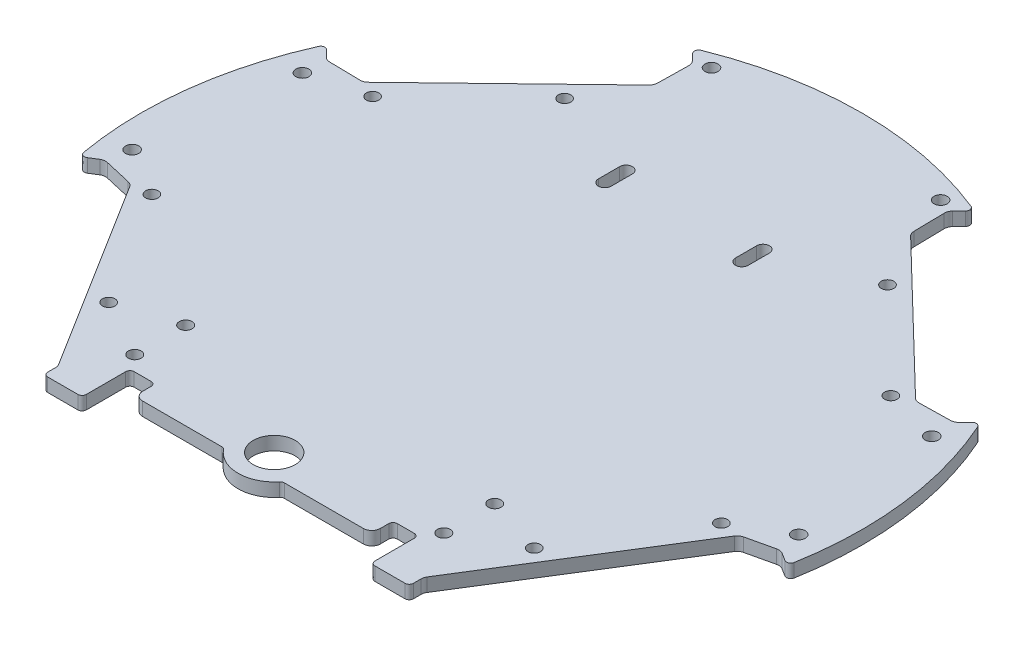
SolidWorks part; units mm, degrees
material "6061 Alloy"
ref_plane "Front Plane" through (0, 0, 0) normal (0, 0, 1) x (1, 0, 0)
ref_plane "Top Plane" through (0, 0, 0) normal (0, 1, 0) x (1, 0, 0)
ref_plane "Right Plane" through (0, 0, 0) normal (1, 0, 0) x (0, 0, -1)
sketch "Sketch1" plane through (0, 0, 0) normal (0, 1, 0) x (1, 0, 0)
  line L0 (0, 0) -> (0, -58.55) construction
  line L1 (-83.4462, -16.178) -> (-71.2857, -8.5793) construction
  line L6 (0, 0) -> (-59.046, 61.1439) construction
  line L7 (0, 0) -> (-72.0841, -45.0431) construction
  line L8 (-33.174, 78.2591) -> (-23.2129, 67.9442) construction
  line L9 (-72.0841, -45.0431) -> (-70.388, -43.9833) construction
  line L10 (-70.388, -43.9833) -> (-84.9608, -20.662) construction
  line L11 (-84.9608, -20.662) -> (-72.2401, -12.7132) construction
  line L12 (-72.2401, -12.7132) -> (-43.0945, -59.3558) construction
  line L13 (-43.0945, -59.3558) -> (-55.8152, -67.3046) construction
  line L14 (-55.8152, -67.3046) -> (-70.388, -43.9833) construction
  line L21 (-59.046, 61.1439) -> (-57.6566, 59.7052)
  line L22 (-77.4385, 40.6021) -> (-37.8748, 78.8083) construction
  line L23 (-73.9694, 32.6911) -> (-77.0537, 35.885)
  line L24 (-37.8748, 78.8083) -> (-27.4549, 68.0182) construction
  line L25 (-27.4549, 68.0182) -> (-67.0186, 29.812) construction
  line L26 (-67.0186, 29.812) -> (-77.4385, 40.6021) construction
  line L27 (-43.0945, -64.8266) -> (-34, -64.8266)
  line L33 (-86.5505, -18.1178) -> (-71.2857, -8.5793) construction
  line L34 (0, 0) -> (0, 50000) construction
  line L35 (0, 0) -> (-50000, 0) construction
  line L36 (-61.619, -58.55) -> (0, -58.55) construction
  line L38 (-67.0927, 25.57) -> (-79.5965, 38.5181) construction
  line L39 (-54.9774, -64.8266) -> (0, -64.8266) construction
  line L40 (-35.7168, 80.8923) -> (-23.2129, 67.9442) construction
  line L41 (-38.9606, -60.3102) -> (-54.2255, -69.8488) construction
  line L42 (-34, -58.55) -> (34, -58.55) construction
  line L43 (-43.0945, -64.8266) -> (-43.0945, -58.4123)
  line L45 (73.9694, 32.6911) -> (77.0537, 35.885)
  line L46 (-71.2857, -8.5793) -> (-38.9606, -60.3102) construction
  line L47 (83.4462, -16.178) -> (79.6809, -13.8252)
  line L48 (69.4846, -16.1792) -> (43.0945, -58.4123)
  line L49 (43.0945, -64.8266) -> (43.0945, -58.4123)
  line L50 (43.0945, -64.8266) -> (34, -64.8266)
  line L51 (34, -58.55) -> (34, -64.8266)
  line L52 (0, 0) -> (72.0841, -45.0431) construction
  line L53 (0, 0) -> (59.046, 61.1439) construction
  line L54 (-30.0897, 75.0653) -> (-30.2847, 63.8954)
  line L55 (-62.7996, 32.4961) -> (-30.2847, 63.8954)
  line L56 (-30.0897, 75.0653) -> (-33.174, 78.2591)
  line L57 (73.9694, 32.6911) -> (77.0537, 35.885)
  line L58 (30.0897, 75.0653) -> (33.174, 78.2591)
  line L59 (-34, -58.55) -> (-34, -53.55)
  line L60 (62.7996, 32.4961) -> (30.2847, 63.8954)
  line L61 (-73.9694, 32.6911) -> (-62.7996, 32.4961)
  line L62 (-77.0537, 35.885) -> (-67.0927, 25.57) construction
  line L63 (-83.4462, -16.178) -> (-79.6809, -13.8252)
  line L64 (-79.6809, -13.8252) -> (-69.4846, -16.1792)
  line L65 (-69.4846, -16.1792) -> (-43.0945, -58.4123)
  line L66 (-27.4549, 68.0182) -> (-23.2129, 67.9442) construction
  line L67 (-72.2401, -12.7132) -> (-71.2857, -8.5793) construction
  line L68 (30.0897, 75.0653) -> (30.2847, 63.8954)
  line L69 (73.9694, 32.6911) -> (62.7996, 32.4961)
  line L70 (-34, -58.55) -> (-34, -64.8266)
  line L71 (79.6809, -13.8252) -> (69.4846, -16.1792)
  line L72 (-34, -53.55) -> (-28, -53.55)
  line L73 (-28, -53.55) -> (-28, -58.55)
  line L74 (-28, -58.55) -> (28, -58.55)
  line L75 (28, -53.55) -> (28, -58.55)
  line L76 (34, -53.55) -> (28, -53.55)
  line L77 (34, -58.55) -> (34, -53.55)
  line L97 (-23.2129, 67.9442) -> (-67.0927, 25.57) construction
  circle A0 centre (0, 0) radius 85 construction
  circle A1 centre (0, 0) radius 90 construction
  arc A51 (-77.0537, 35.885) -> (-83.4462, -16.178) centre (0, 0) ccw
  arc A52 (77.0537, 35.885) -> (83.4462, -16.178) centre (0, 0) cw
  arc A54 (-33.174, 78.2591) -> (33.174, 78.2591) centre (0, 0) cw
  point P29 (-31.6318, 76.6622)
  point P33 (-47.2368, 48.9151)
  point P34 (31.6318, 76.6622)
  point P35 (-57.6673, -36.0345)
  point P85 (-57.6566, 59.7052)
  dimension "D2" = 58
  dimension "D12" = 170
  dimension "D14" = 34
  dimension "D15" = 3
  dimension "D3" = 180
  dimension "D4" = 64.8266
  dimension "D5" = 44
  dimension "D6" = 15
  dimension "D7" = 55
  dimension "D8" = 58.55
  dimension "D9" = 2
  dimension "D11" = 2
  dimension "D16" = 7
  dimension "D17" = 7
  dimension "D18" = 0.5
  dimension "D19" = 1
  dimension "D20" = 6
  dimension "D21" = 5
extrude "Boss-Extrude4" add sketch "Sketch1" along normal blind 3.175 contours A0 L70 region at (0, 0, -6.6852)
ref_point "Rear_Axle_Center (L)"
ref_axis "Rear_Axle_Proj (L)" through (46.5421, 0, -48.1958) along (0, 1, 0)
ref_point "Front_Axle_Center (L)"
ref_axis "Front_Axle_Proj (L)" through (57.2432, 0, 35.7696) along (0, 1, 0)
ref_point "Front_Axle_Center (R)"
ref_axis "Front_Axle_Proj (R)" through (-57.2432, 0, 35.7696) along (0, 1, 0)
ref_point "Read_Axle_Center (R)"
ref_axis "Rear_Axle_Proj (R)" through (-46.5421, 0, -48.1958) along (0, 1, 0)
sketch "Sketch17" plane through (0, 3.175, 0) normal (0, 1, 0) x (1, 0, 0)
  line L0 (0, -53.55) -> (0, -58.55) construction
  line L1 (-28, -58.55) -> (28, -58.55) construction
  circle A0 centre (0, -53.55) radius 8.5
  dimension "D1" = 17
  dimension "D2" = 5
extrude "Boss-Extrude5" add sketch "Sketch17" against normal up to surface (3.175 mm away) up to face at (0, 0, 5.182)
ref_plane "Plane1" through (0, 0, 10) normal (0, 0, 1) x (1, 0, 0)
hole_wizard "M3 Clearance Hole3" positions "Sketch18" profile "Sketch19" hole size "M3" standard "ANSI Metric" end condition through all
sketch "Sketch18" plane through (0, 0, 0) normal (0, -1, 0) x (-1, 0, 0)
  line L0 (-36.415, -50) -> (-36.415, -38) construction
  line L3 (0, 0) -> (0, -38) construction
  line L4 (36.415, -50) -> (36.415, -38) construction
  line L6 (0, -38) -> (36.415, -38) construction
  line L8 (0, -38) -> (-36.415, -38) construction
  point P1 (36.415, -50)
  point P3 (36.415, -38)
  point P5 (-36.415, -50)
  point P33 (-36.415, -38)
  dimension "D1" = 12
  dimension "D2" = 36.415
  dimension "D3" = 36.415
  dimension "D4" = 38
sketch "Sketch19" plane through (-36.415, 0, 50) normal (1, 0, 0) x (0, 0, -1)
  line L0 (0, 0) -> (0, 3.175)
  line L1 (0, 3.175) -> (1.5, 3.175)
  line L2 (1.5, 3.175) -> (1.5, 0)
  line L5 (1.5, 0) -> (0, 0)
  line L11 (0, -6.35) -> (0, 107.95) construction
  dimension "Thru Hole Dia." = 3
  dimension "Thru Hole Depth" = 3.175
hole_wizard "M3 Clearance Hole1" positions "Sketch11" profile "Sketch12" hole size "M3" standard "ANSI Metric" end condition through all
sketch "Sketch11" plane through (0, 3.175, 0) normal (0, 1, 0) x (1, 0, 0)
  line L0 (83.4462, -16.178) -> (79.6809, -13.8252) construction
  line L2 (73.9694, 32.6911) -> (77.0537, 35.885) construction
  line L4 (-73.9694, 32.6911) -> (-77.0537, 35.885) construction
  line L6 (0, 0) -> (0, -50000) construction
  line L7 (78.4111, 9.6277) -> (84.3664, 10.3589) construction
  line L10 (74.155, 27.2403) -> (78.5423, -8.4914) construction
  line L12 (78.4111, 9.6277) -> (76.3487, 9.3744) construction
  arc A7 (77.964, -12.7523) -> (72.563, 31.2347) centre (0, 0) ccw construction
  arc A13 (-77.964, -12.7523) -> (-72.563, 31.2347) centre (0, 0) cw construction
  arc A17 (83.4462, -16.178) -> (77.0537, 35.885) centre (0, 0) ccw construction
  point P34 (78.5423, -8.4914)
  point P66 (74.155, 27.2403)
  point P70 (-74.155, 27.2403)
  point P71 (-78.5423, -8.4914)
  dimension "D1" = 6
  dimension "D2" = 36
sketch "Sketch12" plane through (-78.5423, 3.175, 8.4914) normal (1, 0, 0) x (0, 0, 1)
  line L0 (0, 0) -> (0, 3.175)
  line L1 (0, 3.175) -> (1.55, 3.175)
  line L2 (1.55, 3.175) -> (1.55, 0)
  line L5 (1.55, 0) -> (0, 0)
  line L11 (0, -6.35) -> (0, 107.95) construction
  dimension "Thru Hole Dia." = 3.1
  dimension "Thru Hole Depth" = 3.175
hole_wizard "M3 Clearance Hole4" positions "Sketch9" profile "Sketch10" hole size "M3" standard "ANSI Metric" end condition through all
sketch "Sketch9" plane through (0, 0, 0) normal (0, -1, 0) x (-1, 0, 0)
  line L0 (0, 0) -> (0, 63.4318) construction
  line L1 (-38.0437, 52.9272) -> (38.0437, 52.9272) construction
  line L3 (61.0625, 30.6981) -> (-61.0625, 30.6981) construction
  line L4 (-67.0993, -15.2789) -> (67.0993, -15.2789) construction
  line L5 (50.1419, -42.4164) -> (-50.1419, -42.4164) construction
  line L6 (-61.0625, 30.6981) -> (-38.0437, 52.9272) construction
  line L7 (38.0437, 52.9272) -> (61.0625, 30.6981) construction
  line L8 (67.0993, -15.2789) -> (50.1419, -42.4164) construction
  line L9 (-50.1419, -42.4164) -> (-67.0993, -15.2789) construction
  line L10 (0, 0) -> (-44.8055, 46.3974) construction
  line L11 (0, 0) -> (44.8055, 46.3974) construction
  line L12 (0, 0) -> (-96.9468, 0) construction
  line L14 (-55.1231, -34.4448) -> (0, 0) construction
  line L15 (0, 0) -> (55.1231, -34.4448) construction
  line L18 (-69.4846, -16.1792) -> (-43.0945, -58.4123) construction
  line L19 (-62.7996, 32.4961) -> (-30.2847, 63.8954) construction
  point P0 (-67.0993, -15.2789)
  point P2 (-50.1419, -42.4164)
  point P9 (-61.0625, 30.6981)
  point P11 (-38.0437, 52.9272)
  point P30 (50.1419, -42.4164)
  point P31 (67.0993, -15.2789)
  point P32 (38.0437, 52.9272)
  point P33 (61.0625, 30.6981)
  dimension "D9" = 46
  dimension "D10" = 46
  dimension "D11" = 32
  dimension "D12" = 32
  dimension "D7" = 58
  dimension "D5" = 32
  dimension "D6" = 2.5
  dimension "D8" = 9.4
  dimension "D2" = 44
  dimension "D3" = 32
  dimension "D4" = 2.5
  dimension "D13" = 9.4
sketch "Sketch10" plane through (67.0993, 0, 15.2789) normal (1, 0, 0) x (0, 0, -1)
  line L0 (0, 0) -> (0, 3.175)
  line L1 (0, 3.175) -> (1.475, 3.175)
  line L2 (1.475, 3.175) -> (1.475, 0)
  line L5 (1.475, 0) -> (0, 0)
  line L11 (0, -6.35) -> (0, 107.95) construction
  dimension "Thru Hole Dia." = 2.95
  dimension "Thru Hole Depth" = 3.175
hole_wizard "M3 Clearance Hole2" positions "Sketch13" profile "Sketch14" hole size "M3" standard "ANSI Metric" end condition through all
sketch "Sketch13" plane through (0, 3.175, 0) normal (0, 1, 0) x (1, 0, 0)
  line L0 (0, 0) -> (0, 85) construction
  line L2 (-24, 47) -> (-24, 81) construction
  line L3 (-24, 47) -> (24, 47) construction
  line L4 (-24, 81) -> (24, 81) construction
  line L5 (24, 47) -> (24, 81) construction
  line L6 (-24, 47) -> (24, 81) construction
  line L7 (-24, 81) -> (24, 47) construction
  line L8 (-38.0437, 52.9272) -> (-61.0625, 30.6981) construction
  line L10 (-36.307, 51.1289) -> (-59.3259, 28.8998) construction
  line L11 (-16.3488, 39.8187) -> (-31.6313, 55.6441) construction
  line L12 (-16.3488, 39.8187) -> (-48.7191, 8.559) construction
  line L13 (-31.6313, 55.6441) -> (-64.0016, 24.3845) construction
  line L14 (-48.7191, 8.559) -> (-64.0016, 24.3845) construction
  line L15 (-16.3488, 39.8187) -> (-64.0016, 24.3845) construction
  line L16 (-31.6313, 55.6441) -> (-48.7191, 8.559) construction
  line L17 (-49.5531, 41.8127) -> (-40.1752, 32.1016) construction
  line L18 (-27, 76.4978) -> (-27, 80.5978) construction
  arc A0 (33.174, 78.2591) -> (-33.174, 78.2591) centre (0, 0) ccw construction
  circle A1 centre (-16.2162, 44) radius 3 construction
  circle A2 centre (-27, 76.4978) radius 3 construction
  point P65 (0, 64)
  point P181 (-27, 76.4978)
  point P184 (27, 76.4978)
  dimension "D7" = 6
  dimension "D1" = 48
  dimension "D2" = 34
  dimension "D3" = 4
  dimension "D5" = 45
  dimension "D6" = 22
  dimension "D8" = 4.1
  dimension "D4" = 2.5
sketch "Sketch14" plane through (27, 3.175, -76.4978) normal (1, 0, 0) x (0, 0, 1)
  line L0 (0, 0) -> (0, 3.175)
  line L1 (0, 3.175) -> (1.55, 3.175)
  line L2 (1.55, 3.175) -> (1.55, 0)
  line L5 (1.55, 0) -> (0, 0)
  line L11 (0, -6.35) -> (0, 107.95) construction
  dimension "Thru Hole Dia." = 3.1
  dimension "Thru Hole Depth" = 3.175
sketch "Sketch20" plane through (0, 3.175, 0) normal (0, 1, 0) x (1, 0, 0)
  line L0 (-16.1485, 45.5) -> (-16.1485, 40.5) construction
  line L1 (-14.6485, 45.5) -> (-14.6485, 40.5)
  line L2 (-17.6485, 45.5) -> (-17.6485, 40.5)
  line L3 (0, 0) -> (0, 85) construction
  line L5 (16.1485, 45.5) -> (16.1485, 40.5) construction
  line L6 (14.6485, 45.5) -> (14.6485, 40.5)
  line L7 (17.6485, 45.5) -> (17.6485, 40.5)
  arc A0 (-14.6485, 45.5) -> (-17.6485, 45.5) centre (-16.1485, 45.5) ccw
  arc A1 (-17.6485, 40.5) -> (-14.6485, 40.5) centre (-16.1485, 40.5) ccw
  arc A5 (33.174, 78.2591) -> (-33.174, 78.2591) centre (0, 0) ccw construction
  arc A7 (14.6485, 45.5) -> (17.6485, 45.5) centre (16.1485, 45.5) cw
  arc A8 (17.6485, 40.5) -> (14.6485, 40.5) centre (16.1485, 40.5) cw
  point P2 (-16.1485, 43)
  point P16 (16.1485, 43)
  dimension "D1" = 45.5
  dimension "D2" = 3
  dimension "D3" = 5
  dimension "D4" = 16.1485
extrude "Cut-Extrude1" cut sketch "Sketch20" against normal through all
sketch "Sketch22" plane through (0, 3.175, 0) normal (0, 1, 0) x (1, 0, 0)
  line L0 (-56.2896, -37.2958) -> (-57.6464, -38.1436) construction
  line L1 (-69.4846, -16.1792) -> (-43.0945, -58.4123) construction
  line L2 (-43.0945, -64.8266) -> (-43.0945, -58.4123) construction
  line L3 (30.2452, 66.1578) -> (65.062, 32.5356)
  line L4 (71.6894, -15.6702) -> (43.0945, -61.4316)
  line L28 (-30.2452, 66.1578) -> (-65.062, 32.5356)
  line L29 (-71.6894, -15.6702) -> (-43.0945, -61.4316)
  line L30 (-79.6809, -13.8252) -> (-69.4846, -16.1792) construction
  line L31 (0, 85) -> (0, -53.55) construction
  line L32 (-46.5421, 48.1958) -> (-47.6536, 49.3467) construction
  line L56 (-28, -58.55) -> (-6.8739, -58.55)
  line L57 (6.8739, -58.55) -> (28, -58.55)
  line L58 (28, -58.55) -> (28, -53.55)
  line L59 (28, -53.55) -> (34, -53.55)
  line L60 (34, -53.55) -> (34, -64.8266)
  line L61 (34, -64.8266) -> (43.0945, -64.8266)
  line L62 (43.0945, -64.8266) -> (43.0945, -58.4123)
  line L63 (43.0945, -58.4123) -> (69.4846, -16.1792)
  line L64 (69.4846, -16.1792) -> (79.6809, -13.8252)
  line L65 (79.6809, -13.8252) -> (83.4462, -16.178)
  line L66 (77.0537, 35.885) -> (73.9694, 32.6911)
  line L67 (73.9694, 32.6911) -> (62.7996, 32.4961)
  line L68 (62.7996, 32.4961) -> (30.2847, 63.8954)
  line L69 (30.2847, 63.8954) -> (30.0897, 75.0653)
  line L70 (30.0897, 75.0653) -> (33.174, 78.2591)
  line L71 (-33.174, 78.2591) -> (-30.0897, 75.0653)
  line L72 (-30.0897, 75.0653) -> (-30.2847, 63.8954)
  line L73 (-30.2847, 63.8954) -> (-62.7996, 32.4961)
  line L74 (-62.7996, 32.4961) -> (-73.9694, 32.6911)
  line L75 (-73.9694, 32.6911) -> (-77.0537, 35.885)
  line L76 (-83.4462, -16.178) -> (-79.6809, -13.8252)
  line L77 (-79.6809, -13.8252) -> (-69.4846, -16.1792)
  line L78 (-69.4846, -16.1792) -> (-43.0945, -58.4123)
  line L79 (-43.0945, -58.4123) -> (-43.0945, -64.8266)
  line L80 (-43.0945, -64.8266) -> (-34, -64.8266)
  line L81 (-34, -64.8266) -> (-34, -53.55)
  line L82 (-34, -53.55) -> (-28, -53.55)
  line L83 (-28, -53.55) -> (-28, -58.55)
  line L84 (-28, -58.55) -> (-6.8739, -58.55)
  line L85 (6.8739, -58.55) -> (28, -58.55)
  line L86 (28, -58.55) -> (28, -53.55)
  line L87 (28, -53.55) -> (34, -53.55)
  line L88 (34, -53.55) -> (34, -64.8266)
  line L89 (34, -64.8266) -> (43.0945, -64.8266)
  line L90 (43.0945, -64.8266) -> (43.0945, -58.4123)
  line L91 (43.0945, -58.4123) -> (69.4846, -16.1792)
  line L92 (69.4846, -16.1792) -> (79.6809, -13.8252)
  line L93 (79.6809, -13.8252) -> (83.4462, -16.178)
  line L94 (77.0537, 35.885) -> (73.9694, 32.6911)
  line L95 (73.9694, 32.6911) -> (62.7996, 32.4961)
  line L96 (62.7996, 32.4961) -> (30.2847, 63.8954)
  line L97 (30.2847, 63.8954) -> (30.0897, 75.0653)
  line L98 (30.0897, 75.0653) -> (33.174, 78.2591)
  line L99 (-33.174, 78.2591) -> (-30.0897, 75.0653)
  line L100 (-30.0897, 75.0653) -> (-30.2847, 63.8954)
  line L101 (-30.2847, 63.8954) -> (-62.7996, 32.4961)
  line L102 (-62.7996, 32.4961) -> (-73.9694, 32.6911)
  line L103 (-73.9694, 32.6911) -> (-77.0537, 35.885)
  line L104 (-83.4462, -16.178) -> (-79.6809, -13.8252)
  line L105 (-79.6809, -13.8252) -> (-69.4846, -16.1792)
  line L106 (-69.4846, -16.1792) -> (-43.0945, -58.4123)
  line L107 (-43.0945, -58.4123) -> (-43.0945, -64.8266)
  line L108 (-43.0945, -64.8266) -> (-34, -64.8266)
  line L109 (-34, -64.8266) -> (-34, -53.55)
  line L110 (-34, -53.55) -> (-28, -53.55)
  line L111 (-28, -53.55) -> (-28, -58.55)
  arc A8 (-6.8739, -58.55) -> (6.8739, -58.55) centre (0, -53.55) ccw
  arc A9 (83.4462, -16.178) -> (77.0537, 35.885) centre (0, 0) ccw
  arc A10 (33.174, 78.2591) -> (-33.174, 78.2591) centre (0, 0) ccw
  arc A11 (-77.0537, 35.885) -> (-83.4462, -16.178) centre (0, 0) ccw
  arc A12 (-6.8739, -58.55) -> (6.8739, -58.55) centre (0, -53.55) ccw
  arc A13 (83.4462, -16.178) -> (77.0537, 35.885) centre (0, 0) ccw
  arc A14 (33.174, 78.2591) -> (-33.174, 78.2591) centre (0, 0) ccw
  arc A15 (-77.0537, 35.885) -> (-83.4462, -16.178) centre (0, 0) ccw
  dimension "D2" = 1.6
  dimension "D1" = 0
extrude "Boss-Extrude6" add sketch "Sketch22" against normal up to surface (3.175 mm away) contours L102 L101 L100 L28 | L107 L106 L105 L29 | L92 L91 L90 L4 | L97 L96 L95 L3 region at (47.1042, 3.175, -48.7778) region at (-47.1042, 3.175, -48.7778) region at (56.8481, 3.175, 37.9317) region at (-56.8481, 3.175, 37.9317) up to face at (-16.1485, 0, -43)
fillet "Fillet1" radius 2 16 edges at (-30.0897, 1.5875, -75.0653) (30.0897, 1.5875, -75.0653) (-79.6809, 1.5875, 13.8252) (79.6809, 1.5875, 13.8252) (73.9694, 1.5875, -32.6911) (-73.9694, 1.5875, -32.6911) (28, 1.5875, 58.55) (-28, 1.5875, 58.55) (65.062, 1.5875, -32.5356) (30.2452, 1.5875, -66.1578) (71.6894, 1.5875, 15.6702) (43.0945, 1.5875, 61.4316) (-43.0945, 1.5875, 61.4316) (-71.6894, 1.5875, 15.6702) (-65.062, 1.5875, -32.5356) (-30.2452, 1.5875, -66.1578)
fillet "Fillet3" radius 1 16 edges at (-77.0537, 1.5875, -35.885) (77.0537, 1.5875, -35.885) (83.4462, 1.5875, 16.178) (43.0945, 1.5875, 64.8266) (34, 1.5875, 64.8266) (-34, 1.5875, 64.8266) (-43.0945, 1.5875, 64.8266) (-33.174, 1.5875, -78.2591) (33.174, 1.5875, -78.2591) (-83.4462, 1.5875, 16.178) (28, 1.5875, 53.55) (34, 1.5875, 53.55) (-28, 1.5875, 53.55) (-34, 1.5875, 53.55) (-6.8739, 1.5875, 58.55) (6.8739, 1.5875, 58.55)
sketch "Sketch23" plane through (0, 3.175, 0) normal (0, 1, 0) x (1, 0, 0)
  circle A0 centre (0, -53.55) radius 4.95
  dimension "D1" = 9.9
extrude "Cut-Extrude2" cut sketch "Sketch23" against normal through all
equation "\"D3@Sketch18\"=\"D2@Sketch18\""
equation "\"D2@Sketch18\"=72.83/2"
equation "\"D3@Sketch9\"=\"D5@Sketch9\""
equation "\"D4@Sketch9\"=\"D6@Sketch9\""
equation "\"D13@Sketch9\"=\"D8@Sketch9\""
